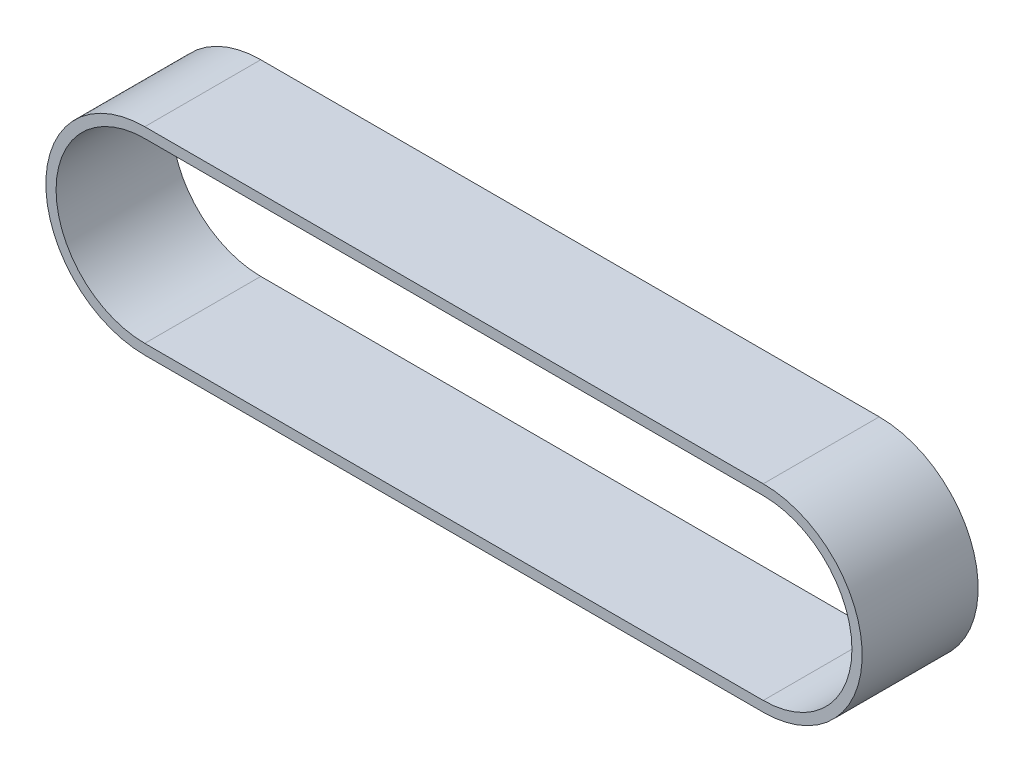
SolidWorks part; units mm, degrees
material "Rubber"
ref_plane "Front Plane" through (0, 0, 0) normal (0, 0, 1) x (1, 0, 0)
ref_plane "Top Plane" through (0, 0, 0) normal (0, 1, 0) x (1, 0, 0)
ref_plane "Right Plane" through (0, 0, 0) normal (1, 0, 0) x (0, 0, -1)
sketch "Sketch1" plane through (0, 0, 0) normal (0, 0, 1) x (1, 0, 0)
  line L0 (-47.5872, -1.789) -> (43.055, -1.789) construction
  line L1 (-47.5872, 11.211) -> (43.055, 11.211)
  line L2 (-47.5872, -14.789) -> (43.055, -14.789)
  line L3 (-47.5872, 12.711) -> (43.055, 12.711)
  line L4 (-47.5872, -16.289) -> (43.055, -16.289)
  arc A0 (-47.5872, 11.211) -> (-47.5872, -14.789) centre (-47.5872, -1.789) ccw
  arc A1 (43.055, -14.789) -> (43.055, 11.211) centre (43.055, -1.789) ccw
  arc A2 (43.055, -16.289) -> (43.055, 12.711) centre (43.055, -1.789) ccw
  arc A3 (-47.5872, 12.711) -> (-47.5872, -16.289) centre (-47.5872, -1.789) ccw
  point P2 (-2.2661, -1.789)
  dimension "D1" = 13
  dimension "D2" = 1.5
extrude "Boss-Extrude1" add sketch "Sketch1" along normal blind 17
